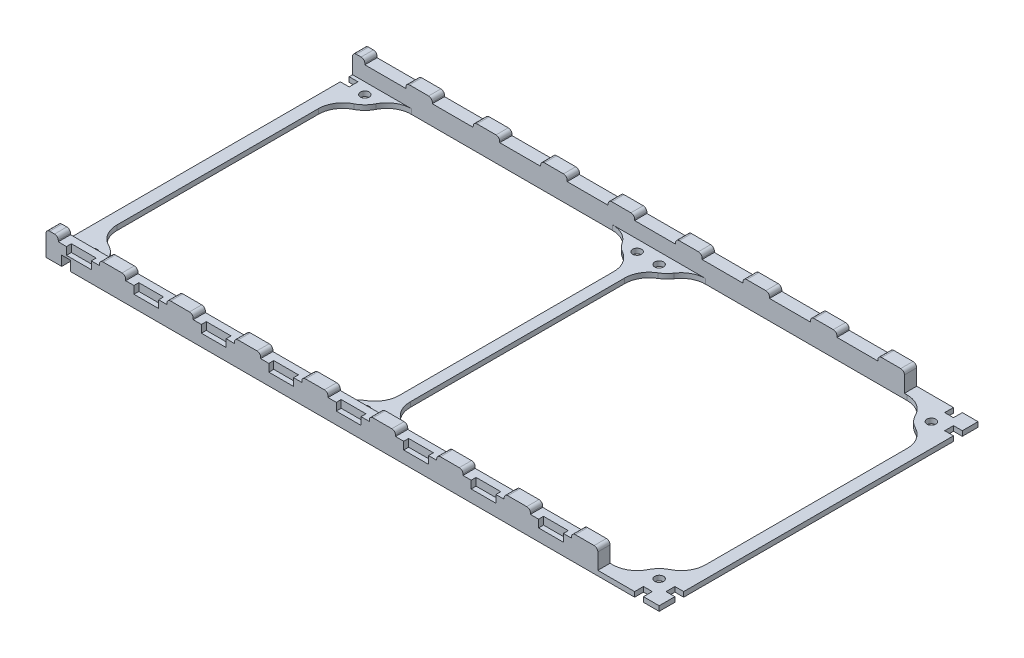
SolidWorks part; units mm, degrees
ref_plane "Front Plane" through (0, 0, 0) normal (0, 0, 1) x (1, 0, 0)
ref_plane "Top Plane" through (0, 0, 0) normal (0, 1, 0) x (1, 0, 0)
ref_plane "Right Plane" through (0, 0, 0) normal (1, 0, 0) x (0, 0, -1)
sketch "Sketch1" plane through (0, 0, 0) normal (0, 1, 0) x (1, 0, 0)
  line L1 (0, 0) -> (250, 0)
  line L2 (0, 0) -> (0, 130)
  line L3 (0, 130) -> (250, 130)
  line L4 (250, 0) -> (250, 130)
  line L5 (5, 5) -> (245, 5)
  line L6 (5, 5) -> (5, 125)
  line L7 (5, 125) -> (245, 125)
  line L8 (245, 5) -> (245, 125)
  dimension "D1" = 250
  dimension "D2" = 130
  dimension "D3" = 240
  dimension "D4" = 120
  dimension "D5" = 5
  dimension "D6" = 5
extrude "Boss-Extrude1" add sketch "Sketch1" along normal blind 2
sketch "Sketch2" plane through (0, 0, 0) normal (0, 1, 0) x (1, 0, 0)
  line L0 (245, 125) -> (5, 125) construction
  line L1 (5, 5) -> (14, 5)
  line L2 (5, 5) -> (5, 14)
  line L3 (5, 14) -> (14, 14)
  line L4 (14, 5) -> (14, 14)
  line L5 (5, 125) -> (14, 125)
  line L6 (5, 125) -> (5, 116)
  line L7 (5, 116) -> (14, 116)
  line L8 (14, 125) -> (14, 116)
  line L9 (116, 125) -> (125, 125)
  line L10 (116, 125) -> (116, 116)
  line L11 (116, 116) -> (125, 116)
  line L14 (5, 5) -> (245, 5) construction
  line L15 (125, 116) -> (134, 116)
  line L17 (125, 125) -> (134, 125)
  line L18 (134, 116) -> (134, 125)
  line L19 (116, 5) -> (134, 5)
  line L20 (116, 5) -> (116, 14)
  line L21 (116, 14) -> (134, 14)
  line L22 (134, 5) -> (134, 14)
  line L24 (245, 125) -> (236, 125)
  line L25 (245, 125) -> (245, 116)
  line L26 (245, 116) -> (236, 116)
  line L27 (236, 125) -> (236, 116)
  line L28 (245, 5) -> (236, 5)
  line L29 (245, 5) -> (245, 14)
  line L30 (245, 14) -> (236, 14)
  line L31 (236, 5) -> (236, 14)
  circle A0 centre (9.5, 9.5) radius 1.8
  circle A1 centre (9.5, 120.5) radius 1.8
  circle A2 centre (120.5, 120.5) radius 1.8
  circle A3 centre (129.5, 120.5) radius 1.8
  circle A4 centre (120.5, 9.5) radius 1.8
  circle A5 centre (129.5, 9.5) radius 1.8
  circle A6 centre (240.5, 120.5) radius 1.8
  circle A7 centre (240.5, 9.5) radius 1.8
  dimension "D9" = 3.6
  dimension "D10" = 3.6
  dimension "D12" = 3.6
  dimension "D18" = 3.6
  dimension "D16" = 3.6
  dimension "D23" = 3.6
  dimension "D27" = 3.6
  dimension "D32" = 3.6
  dimension "D2" = 4.5
  dimension "D3" = 4.5
  dimension "D4" = 4.5
  dimension "D5" = 4.5
  dimension "D6" = 4.5
  dimension "D7" = 4.5
  dimension "D8" = 4.5
  dimension "D11" = 4.5
  dimension "D13" = 4.5
  dimension "D14" = 4.5
  dimension "D15" = 4.5
  dimension "D17" = 4.5
  dimension "D19" = 4.5
  dimension "D20" = 4.5
  dimension "D21" = 4.5
  dimension "D22" = 4.5
  dimension "D24" = 9
  dimension "D25" = 4.5
  dimension "D26" = 120
  dimension "D28" = 4.5
  dimension "D29" = 4.5
  dimension "D30" = 4.5
  dimension "D31" = 4.5
  dimension "D33" = 4.5
  dimension "D34" = 4.5
  dimension "D35" = 4.5
  dimension "D36" = 4.5
extrude "Boss-Extrude2" add sketch "Sketch2" along normal blind 2
fillet "Fillet1" radius 10 12 edges at (5, 1, -14) (14, 1, -5) (5, 1, -116) (14, 1, -125) (116, 1, -125) (134, 1, -125) (245, 1, -116) (236, 1, -125) (245, 1, -14) (236, 1, -5) (116, 1, -5) (134, 1, -5)
fillet "Fillet2" radius 10 8 edges at (14, 1, -14) (116, 1, -14) (134, 1, -14) (236, 1, -14) (236, 1, -116) (134, 1, -116) (116, 1, -116) (14, 1, -116)
sketch "Sketch3" plane through (0, 0, 0) normal (0, 1, 0) x (1, 0, 0)
  line L1 (122.7534, 116) -> (127.2466, 116)
  line L2 (122.7534, 116) -> (122.7534, 14)
  line L3 (122.7534, 14) -> (127.2466, 14)
  line L4 (127.2466, 116) -> (127.2466, 14)
extrude "Boss-Extrude3" add sketch "Sketch3" along normal blind 2
fillet "Fillet3" radius 10 4 edges at (122.7534, 1, -116) (127.2466, 1, -116) (127.2466, 1, -14) (122.7534, 1, -14)
sketch "Sketch4" plane through (0, 2, 0) normal (0, 1, 0) x (1, 0, 0)
  line L1 (5, 0) -> (21.8, 0)
  line L2 (5, 0) -> (5, 5)
  line L3 (5, 5) -> (21.8, 5)
  line L4 (21.8, 0) -> (21.8, 5)
  line L5 (5, 130) -> (21.7, 130)
  line L6 (5, 130) -> (5, 125)
  line L7 (5, 125) -> (21.7, 125)
  line L8 (21.7, 130) -> (21.7, 125)
  dimension "D1" = 16.8
  dimension "D2" = 5
  dimension "D3" = 5
  dimension "D4" = 16.7
extrude "Boss-Extrude4" add sketch "Sketch4" along normal blind 6
sketch "Sketch5" plane through (0, 2, 0) normal (0, 1, 0) x (1, 0, 0)
  line L0 (106.0501, 125) -> (23.9499, 125) construction
  line L1 (21.7, 130) -> (32.5, 130)
  line L2 (21.7, 130) -> (21.7, 125)
  line L3 (21.7, 125) -> (32.5, 125)
  line L4 (32.5, 130) -> (32.5, 125)
  line L5 (5, 130) -> (5, 125) construction
  line L6 (21.8, 0) -> (250, 0) construction
  line L7 (21.8, 5) -> (32.5, 5)
  line L8 (21.8, 5) -> (21.8, 0)
  line L9 (21.8, 0) -> (32.5, 0)
  line L10 (32.5, 5) -> (32.5, 0)
  line L11 (5, 5) -> (5, 0) construction
  dimension "D1" = 27.5
  dimension "D2" = 27.5
extrude "Boss-Extrude5" add sketch "Sketch5" along normal blind 8
fillet "Fillet4" radius 1.5 4 edges at (21.8, 10, -2.5) (32.5, 10, -2.5) (32.5, 10, -127.5) (21.7, 10, -127.5)
sketch "Sketch6" plane through (0, 2, 0) normal (0, 1, 0) x (1, 0, 0)
  line L1 (0, 130) -> (5, 130)
  line L2 (0, 130) -> (0, 125)
  line L3 (0, 125) -> (5, 125)
  line L4 (5, 130) -> (5, 125)
  line L5 (0, 0) -> (5, 0)
  line L6 (0, 0) -> (0, 5)
  line L7 (0, 5) -> (5, 5)
  line L8 (5, 0) -> (5, 5)
extrude "Boss-Extrude6" add sketch "Sketch6" along normal blind 8
sketch "Sketch10" plane through (0, 0, 0) normal (0, 0, 1) x (1, 0, 0)
  line L0 (5, 8) -> (21.8, 8) construction
  line L1 (8.35, 8) -> (18.45, 8)
  line L2 (8.35, 8) -> (8.35, 4.9)
  line L3 (8.35, 4.9) -> (18.45, 4.9)
  line L4 (18.45, 8) -> (18.45, 4.9)
  line L6 (5, 10) -> (5, 8) construction
  dimension "D1" = 10.1
  dimension "D2" = 3.1
  dimension "D3" = 3.35
extrude "Cut-Extrude2" cut sketch "Sketch10" against normal blind 2
pattern_linear "LPattern1" count 8 spacing 27.5 along (1, 0, 0) of "Boss-Extrude4", "Boss-Extrude5", "Fillet4"
fillet "Fillet5" radius 1.5 4 edges at (0, 10, -127.5) (5, 10, -127.5) (0, 10, -2.5) (5, 10, -2.5)
sketch "Sketch9" plane through (0, 0, 0) normal (0, 1, 0) x (1, 0, 0)
  line L5 (0, 0) -> (0, 5) construction
  line L7 (10, 3.6) -> (6.4, 3.6)
  line L8 (10, 3.6) -> (10, 0)
  line L9 (10, 0) -> (6.4, 0)
  line L10 (6.4, 3.6) -> (6.4, 0)
  line L11 (1.5, 0) -> (3.5, 0) construction
  line L12 (3.6, 10) -> (0, 10)
  line L13 (3.6, 10) -> (3.6, 6.4)
  line L14 (3.6, 6.4) -> (0, 6.4)
  line L15 (0, 10) -> (0, 6.4)
  line L16 (8.35, 0) -> (18.45, 0) construction
  line L17 (0, 125) -> (0, 5) construction
  point P0 (0, 0)
  dimension "D1" = 3.6
  dimension "D2" = 0
  dimension "D3" = 0
  dimension "D5" = 3.6
  dimension "D6" = 3.6
  dimension "D7" = 10
  dimension "D8" = 3.6
  dimension "D9" = 10
extrude "Cut-Extrude1" cut sketch "Sketch9" along normal blind 4
ref_plane "Plane1" through (125, 0, 0) normal (-1, 0, 0) x (0, 0, 1)
ref_plane "Plane2" through (0, 0, -65) normal (0, 0, 1) x (1, 0, 0)
mirror "Mirror1" about plane through (0, 0, -65) normal (0, 0, 1) of "Cut-Extrude1" second plane through (125, 0, 0) second plane normal (-1, 0, 0)
pattern_linear "LPattern2" count 8 spacing 27.5 along (1, 0, 0) of "Cut-Extrude2"
